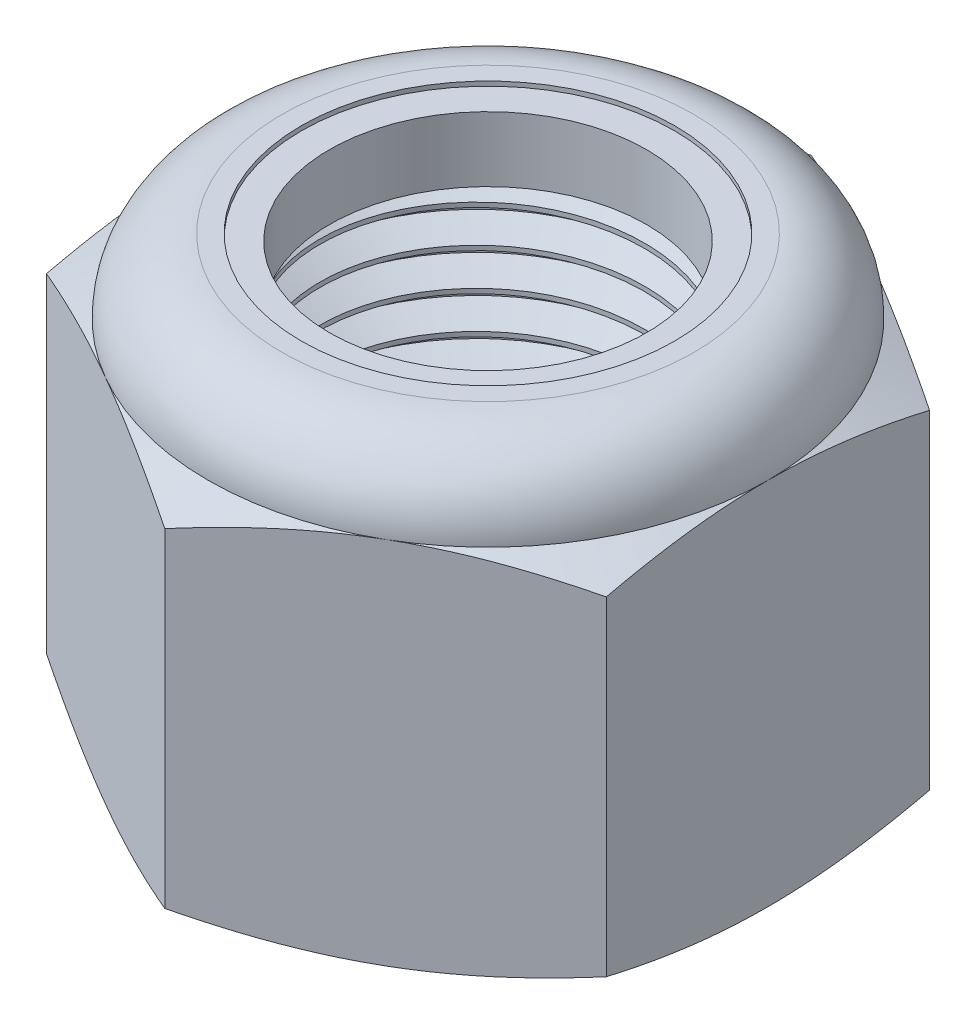
SolidWorks part; units mm, degrees
note: '?' marks a value the reader was unsure of.
ref_plane "Front" through (0, 0, 0) normal (0, 0, 1) x (1, 0, 0)
ref_plane "Top" through (0, 0, 0) normal (0, 1, 0) x (1, 0, 0)
ref_plane "Right" through (0, 0, 0) normal (1, 0, 0) x (0, 0, -1)
sketch "Sketch8" plane through (0, 0, 0) normal (1, 0, 0) x (0, 0, -1)
  line L0 (0, 0) -> (0, 15.0812) construction
  line L1 (9.525, 0) -> (-9.525, 0) construction
  line L2 (-6.35, 15.0812) -> (6.35, 15.0812) construction
  line L3 (6.35, 15.0812) -> (6.35, 13.8112) construction
sketch "Sketch1" plane through (0, 0, 0) normal (0, 1, 0) x (1, 0, 0)
  line L1 (0, 10.9985) -> (-9.525, 5.4993)
  line L2 (-9.525, 5.4993) -> (-9.525, -5.4993)
  line L3 (-9.525, -5.4993) -> (0, -10.9985)
  line L4 (0, -10.9985) -> (9.525, -5.4993)
  line L5 (9.525, -5.4993) -> (9.525, 5.4993)
  line L6 (9.525, 5.4993) -> (0, 10.9985)
  circle A0 centre (0, 0) radius 9.525 construction
  circle A1 centre (0, 0) radius 6.35
extrude "Extrude1" add sketch "Sketch1" along normal up to vertex (15.0813 mm away) up to point (0, 15.0812, 0)
sketch "Sketch5" plane through (0, 0, 0) normal (1, 0, 0) x (0, 0, -1)
  line L0 (0, 0) -> (9.525, 0)
  line L1 (9.525, 0) -> (10.9985, 0.6871)
  line L2 (10.9985, 0.6871) -> (10.9985, 11.8806)
  line L3 (10.9985, 11.8806) -> (9.525, 12.5677)
  line L4 (7.0115, 15.0812) -> (7.0115, 16.3512)
  line L5 (7.0115, 16.3512) -> (12.2685, 16.3512)
  line L6 (12.2685, 16.3512) -> (12.2685, -1.27)
  line L7 (12.2685, -1.27) -> (0, -1.27)
  line L8 (0, -1.27) -> (0, 0)
  line L9 (9.525, 12.5677) -> (9.525, 0) construction
  line L12 (10.9985, 15.0812) -> (10.9985, 0) construction
  line L13 (10.9985, 7.5406) -> (12.2685, 7.5406) construction
  line L15 (0, 0) -> (0, 16.3512) construction
  line L18 (9.525, 0) -> (-9.525, 0) construction
  line L19 (5.4993, 15.0812) -> (10.9985, 15.0812) construction
  line L20 (0, 16.3512) -> (7.0115, 16.3512) construction
  line L21 (5.4993, 0) -> (10.9985, 0) construction
  arc A0 (9.525, 12.5677) -> (7.0115, 15.0812) centre (7.0115, 12.5677) ccw
  dimension "D1" = 25
  dimension "D2" = 1.27
  dimension "D4" = 2.5135
revolve "Cut-Revolve3" cut sketch "Sketch5" angle 360 about L15
sketch "Sketch4" plane through (0, 0, 0) normal (1, 0, 0) x (0, 0, -1)
  line L0 (0, 12.5677) -> (6.985, 12.5677)
  line L1 (6.985, 12.5677) -> (0, 9.3105)
  line L3 (0, 3.2572) -> (6.985, 0)
  line L4 (6.985, 0) -> (0, 0)
  line L5 (0, 0) -> (0, 12.5677) construction
  line L10 (0, 0) -> (0, 15.0812) construction
  line L11 (0, 3.2572) -> (0, 0)
  line L12 (0, 12.5677) -> (0, 9.3105)
  line L13 (8.2489, 12.5677) -> (0, 12.5677) construction
  dimension "D1" = 25
  dimension "D2" = 13.97
sketch "Sketch6" plane through (0, 0, 0) normal (1, 0, 0) x (0, 0, -1)
  line L0 (0, 12.5677) -> (9.3726, 12.5677)
  line L1 (7.0115, 14.9288) -> (3.5057, 14.9288)
  line L2 (0, 16.3512) -> (0, 12.5677)
  line L3 (3.5057, 16.3512) -> (0, 16.3512)
  line L4 (0, 16.3512) -> (7.0115, 16.3512) construction
  line L5 (0, 0) -> (0, 16.3512) construction
  line L6 (0, 16.3512) -> (0, 0) construction
  line L7 (3.5057, 14.9288) -> (3.5057, 16.3512)
  line L8 (7.0115, 15.0812) -> (7.0115, 14.9288) construction
  line L9 (3.5057, 14.9288) -> (0, 14.9288) construction
  line L10 (0, 14.9288) -> (0, 9.3105) construction
  arc A0 (9.3726, 12.5677) -> (7.0115, 14.9288) centre (7.0115, 12.5677) ccw
  arc A1 (9.525, 12.5677) -> (7.0115, 15.0812) centre (7.0115, 12.5677) ccw construction
  dimension "D1" = 0.1524
revolve "Cut-Revolve4" cut sketch "Sketch6" angle 360 about L6
revolve "Cut-Revolve2" cut sketch "Sketch4" angle 360 about L5
sketch "Sketch7" plane through (0, 0, 0) normal (1, 0, 0) x (0, 0, -1)
  line L0 (5.3975, 12.6439) -> (9.2951, 12.6439)
  line L1 (7.0115, 14.8526) -> (5.3975, 14.8526)
  line L2 (5.3975, 14.8526) -> (5.3975, 12.6439)
  line L3 (5.3975, 12.6439) -> (0, 12.6439) construction
  line L4 (0, 12.6439) -> (0, 14.8526) construction
  line L5 (0, 14.8526) -> (5.3975, 14.8526) construction
  line L6 (5.3975, 12.6439) -> (5.3975, 12.5677) construction
  line L7 (0, 12.5677) -> (9.3726, 12.5677) construction
  line L8 (7.0115, 14.8526) -> (7.0115, 14.9288) construction
  arc A0 (9.2951, 12.6439) -> (7.0115, 14.8526) centre (7.0115, 12.5677) ccw
  arc A2 (9.3726, 12.5677) -> (7.0115, 14.9288) centre (7.0115, 12.5677) ccw construction
  dimension "D1" = 0.0762
  dimension "D2" = 10.795
revolve "Revolve2" add sketch "Sketch7" angle 360 about L4
sketch "Sketch2" plane through (0, 0, 0) normal (1, 0, 0) x (0, 0, -1)
  line L0 (-6.35, 0) -> (-6.35, 12.5677) construction
  line L1 (0, 0) -> (6.35, 0)
  line L2 (0, 0) -> (0, 12.5677)
  line L3 (0, 12.5677) -> (6.35, 12.5677)
  line L4 (6.35, 0) -> (6.35, 12.5677)
  line L6 (8.2489, 12.5677) -> (9.525, 12.5677) construction
  line L7 (0, -6.35) -> (0, 0) construction
revolve "Revolve1" add sketch "Sketch2" angle 360 about L7
sketch "Sketch9" plane through (0, 0, 0) normal (1, 0, 0) x (0, 0, -1)
  line L0 (6.4875, 13.7583) -> (6.4875, 12.4883) construction
  line L1 (6.4875, 12.4883) -> (5.3876, 13.1233) construction
  line L2 (5.3876, 13.1233) -> (6.4875, 13.7583) construction
  line L3 (5.5251, 13.2027) -> (5.5251, 13.044) construction
  line L4 (6.35, 13.679) -> (6.35, 12.5677) construction
  line L5 (5.3876, 13.1233) -> (5.5251, 13.1233) construction
  line L6 (6.35, 13.1233) -> (6.4875, 13.1233) construction
  line L7 (6.4187, 13.1233) -> (6.4187, 13.7186) construction
  line L8 (6.4875, 12.4883) -> (6.4187, 13.7186)
  line L9 (6.4187, 13.7186) -> (5.5251, 13.2027)
  line L10 (5.5251, 13.2027) -> (5.5251, 13.044)
  line L11 (5.5251, 13.044) -> (6.4875, 12.4883)
  dimension "D1" = 1.27
  dimension "D2" = 0.1588
sketch "Sketch10" plane through (0, 12.5677, 0) normal (0, 1, 0) x (1, 0, 0)
  circle A1 centre (0, 0) radius 6.35
  circle A2 centre (0, 0) radius 6.35
  dimension "D1" = 0
curve "Helix/Spiral1" pitch 1.27 height 16.3513 turns 12.875
sweep "Cut-Sweep1" cut profiles "Sketch9" path "Helix/Spiral1" align with end faces yes
sketch "Sketch11" plane through (0, 0, 0) normal (1, 0, 0) x (0, 0, -1)
  line L0 (0, 0) -> (0, 15.0812) construction
  line L1 (9.525, 0) -> (-9.525, 0) construction
  line L4 (0, 15.0812) -> (0, 0) construction
  line L5 (0, 7.5406) -> (6.35, 7.5406) construction
  line L6 (0, 0) -> (6.985, 0)
  line L7 (0, 3.2572) -> (0, 0)
  line L8 (6.985, 0) -> (0, 3.2572)
  dimension "D1" = 13.97
  dimension "D2" = 25
revolve "Revolve3" add sketch "Sketch11" angle 360 about L4
sketch "Sketch12" plane through (0, 0, 0) normal (1, 0, 0) x (0, 0, -1)
  line L0 (6.985, 12.5677) -> (0, 12.5677)
  line L1 (0, 12.5677) -> (0, 0)
  line L2 (0, 0) -> (6.985, 0)
  line L3 (9.525, 0) -> (-9.525, 0) construction
  line L4 (6.985, 0) -> (6.985, 12.5677)
  line L5 (-6.985, 0) -> (6.985, 0) construction
revolve "Revolve4" add sketch "Sketch12" angle 360 about L0
combine bodies "Combine1" operation type subtract main body 136 bodies to subtract 133
ref_plane "Contact Plane 1" through (0, 0, 0) normal (0, -1, 0) x (1, 0, 0)
ref_axis "Center Axis 1" through (0, -2.1015, 0) along (0, 1, 0)?
equation "\"D4@Sketch5\"=\"Height@Sketch8\"/6"
equation "\"D1@Sketch9\"=\"Thread Pitch@Sketch8\""
equation "\"D2@Sketch9\"=\"Thread Pitch@Sketch8\"/8"
equation "\"D4@Helix/Spiral1\"=\"Thread Pitch@Sketch8\""
equation "\"D3@Helix/Spiral1\"=\"Thread Pitch@Sketch8\"+\"Height@Sketch8\""
equation "\"D2@Sketch4\"=\"Thread Dia@Sketch8\"*1.1"
equation "\"D1@Sketch11\"=\"Thread Dia@Sketch8\"*1.1"
equation "\"D2@Sketch7\"=\"Thread Dia@Sketch8\"*.85"
